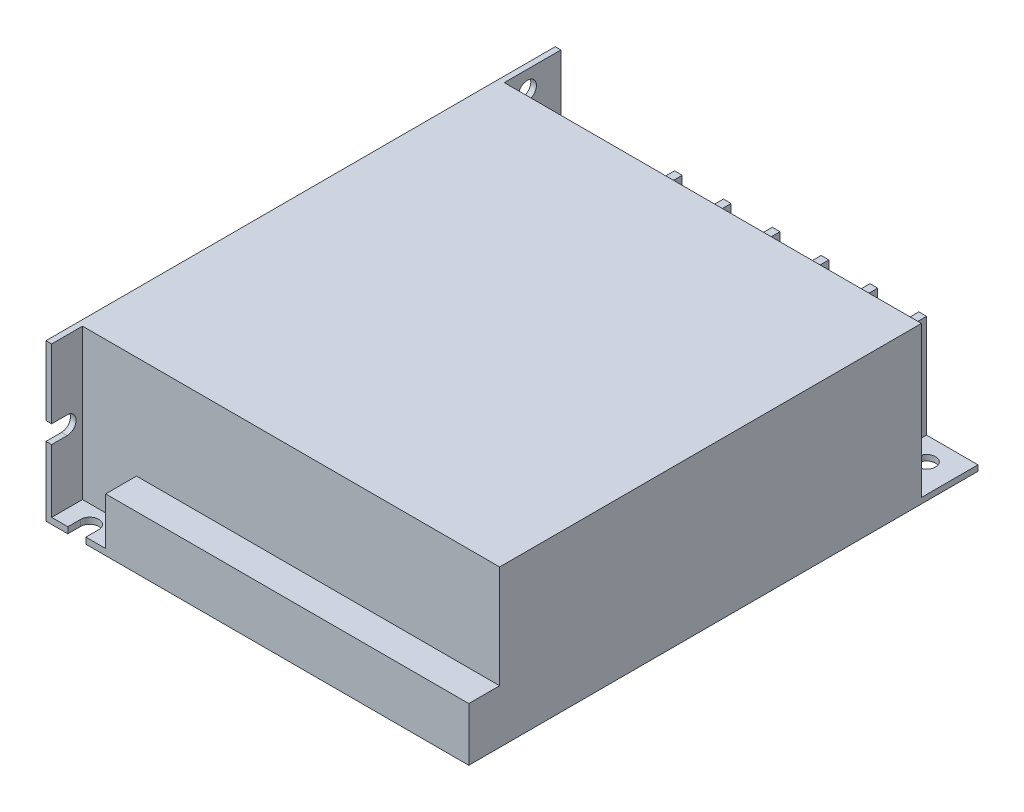
SolidWorks part; units mm, degrees
ref_plane "前基準面" through (0, 0, 0) normal (0, 0, 1) x (1, 0, 0)
ref_plane "上基準面" through (0, 0, 0) normal (0, 1, 0) x (1, 0, 0)
ref_plane "右基準面" through (0, 0, 0) normal (1, 0, 0) x (0, 0, -1)
sketch "草圖1" plane through (0, 0, 0) normal (0, 1, 0) x (1, 0, 0)
  line L1 (0, 0) -> (82.2, 0)
  line L2 (0, 0) -> (0, 99)
  line L3 (0, 99) -> (82.2, 99)
  line L4 (82.2, 0) -> (82.2, 99)
  dimension "D1" = 82.2
  dimension "D2" = 99
extrude "填料-伸長1" add sketch "草圖1" along normal blind 30.4
sketch "草圖3" plane through (0, 30.4, 0) normal (0, 1, 0) x (1, 0, 0)
  line L0 (0, 99) -> (0, 0) construction
  line L1 (82.2, 0) -> (1.1, 0)
  line L2 (82.2, 0) -> (82.2, 6)
  line L3 (82.2, 6) -> (1.1, 6)
  line L4 (1.1, 0) -> (1.1, 6)
  dimension "D1" = 6
  dimension "D2" = 1.1
extrude "除料-伸長1" cut sketch "草圖3" against normal blind 20
sketch "草圖4" plane through (0, 0, 0) normal (0, -1, 0) x (1, 0, 0)
  line L0 (0, -99) -> (0, 0) construction
  line L1 (0, 0) -> (82.2, 0) construction
  line L2 (82.2, -99) -> (0, -99) construction
  circle A0 centre (40.5, -23.5) radius 1.5
  circle A1 centre (40.5, -78.5) radius 1.5
  dimension "D4" = 3
  dimension "D5" = 3
  dimension "D1" = 40.5
  dimension "D2" = 23.5
  dimension "D3" = 20.5
extrude "除料-伸長2" cut sketch "草圖4" against normal blind 3
sketch "草圖5" plane through (0, 0, 0) normal (0, -1, 0) x (1, 0, 0)
  line L0 (82.2, -99) -> (0, -99) construction
  line L1 (82.2, 0) -> (82.2, -99) construction
  circle A0 centre (76.7, -94.5) radius 1.75
  dimension "D3" = 3.5
  dimension "D1" = 4.5
  dimension "D2" = 5.5
extrude "除料-伸長3" cut sketch "草圖5" against normal through all
sketch "草圖6" plane through (0, 30.4, 0) normal (0, 1, 0) x (1, 0, 0)
  line L1 (82.2, 99) -> (1.1, 99)
  line L2 (82.2, 99) -> (82.2, 88)
  line L3 (82.2, 88) -> (1.1, 88)
  line L4 (1.1, 99) -> (1.1, 88)
  line L5 (0, 99) -> (0, 0) construction
  dimension "D1" = 11
  dimension "D2" = 1.1
extrude "除料-伸長4" cut sketch "草圖6" against normal blind 29.3
sketch "草圖7" plane through (0, 0, 0) normal (-1, 0, 0) x (0, 0, 1)
  line L0 (0, 15.2) -> (-99, 15.2) construction
  line L1 (0, 30.4) -> (0, 0) construction
  line L2 (-99, 30.4) -> (-99, 0) construction
  line L3 (-3, 16.95) -> (0, 16.95)
  line L4 (0, 16.95) -> (0, 13.45)
  line L5 (0, 13.45) -> (-3, 13.45)
  circle A0 centre (-89, 15.2) radius 1.75
  circle A1 centre (-15, 15.2) radius 1.75
  arc A2 (-3, 16.95) -> (-3, 13.45) centre (-3, 15.2) ccw
  dimension "D1" = 3.5
  dimension "D2" = 3.5
  dimension "D5" = 3.5
  dimension "D3" = 15
  dimension "D4" = 10
  dimension "D6" = 3
extrude "除料-伸長5" cut sketch "草圖7" against normal blind 3
sketch "草圖8" plane through (0, 1.1, 0) normal (0, 1, 0) x (1, 0, 0)
  line L0 (82.2, 99) -> (1.1, 99) construction
  line L1 (72.2, 99) -> (23.2, 99)
  line L2 (72.2, 99) -> (72.2, 88)
  line L3 (72.2, 88) -> (23.2, 88)
  line L4 (23.2, 99) -> (23.2, 88)
  line L5 (1.1, 88) -> (82.2, 88) construction
  line L6 (82.2, 88) -> (82.2, 99) construction
  dimension "D1" = 49
  dimension "D2" = 10
extrude "填料-伸長2" add sketch "草圖8" along normal blind 20
sketch "草圖9" plane through (0, 1.1, 0) normal (0, 1, 0) x (1, 0, 0)
  line L1 (1.1, 99) -> (23.2, 99)
  line L2 (1.1, 99) -> (1.1, 88)
  line L3 (1.1, 88) -> (23.2, 88)
  line L4 (23.2, 99) -> (23.2, 88)
extrude "填料-伸長3" add sketch "草圖9" along normal blind 5.5
sketch "草圖10" plane through (0, 21.1, 0) normal (0, 1, 0) x (1, 0, 0)
  line L0 (72.2, 99) -> (23.2, 99) construction
  line L1 (24.7, 99) -> (32.7, 99)
  line L2 (24.7, 99) -> (24.7, 88)
  line L3 (24.7, 88) -> (32.7, 88)
  line L4 (32.7, 99) -> (32.7, 88)
  line L6 (34.2, 99) -> (42.2, 99)
  line L7 (34.2, 99) -> (34.2, 88)
  line L8 (34.2, 88) -> (42.2, 88)
  line L9 (42.2, 99) -> (42.2, 88)
  line L10 (43.7, 99) -> (51.7, 99)
  line L11 (43.7, 99) -> (43.7, 88)
  line L12 (43.7, 88) -> (51.7, 88)
  line L13 (51.7, 99) -> (51.7, 88)
  line L14 (53.2, 99) -> (61.2, 99)
  line L15 (53.2, 99) -> (53.2, 88)
  line L16 (53.2, 88) -> (61.2, 88)
  line L17 (61.2, 99) -> (61.2, 88)
  line L18 (62.7, 99) -> (70.7, 99)
  line L19 (62.7, 99) -> (62.7, 88)
  line L20 (62.7, 88) -> (70.7, 88)
  line L21 (70.7, 99) -> (70.7, 88)
  line L23 (82.2, 88) -> (1.1, 88)
  line L24 (23.2, 99) -> (23.2, 88) construction
  line M23 (72.2, 99) -> (23.2, 99)
  line M25 (23.2, 88) -> (72.2, 88)
  dimension "D1" = 8
  dimension "D2" = 8
  dimension "D3" = 8
  dimension "D4" = 8
  dimension "D5" = 8
  dimension "D6" = 1.5
  dimension "D7" = 1.5
  dimension "D8" = 1.5
  dimension "D9" = 1.5
  dimension "D10" = 1.5
extrude "除料-伸長6" cut sketch "草圖10" against normal blind 8 contours L21 L19 M23 M25 | L17 L15 M23 M25 | L13 L11 M23 M25 | L9 L7 M23 M25 | L4 L2 M23 M25 region at (28.7, 21.1, -93.5) region at (38.2, 21.1, -93.5) region at (47.7, 21.1, -93.5) region at (57.2, 21.1, -93.5) region at (66.7, 21.1, -93.5)
sketch "草圖11" plane through (0, 13.1, 0) normal (0, 1, 0) x (1, 0, 0)
  line L0 (62.7, 88) -> (70.7, 99) construction
  line L1 (53.2, 88) -> (61.2, 99) construction
  line L2 (70.7, 88) -> (62.7, 99) construction
  line L3 (53.2, 99) -> (61.2, 88) construction
  line L5 (43.7, 88) -> (51.7, 99) construction
  line L7 (43.7, 99) -> (51.7, 88) construction
  line L10 (34.2, 99) -> (42.2, 88) construction
  line L12 (34.2, 88) -> (42.2, 99) construction
  line L14 (24.7, 99) -> (32.7, 88) construction
  line L16 (24.7, 88) -> (32.7, 99) construction
  circle A0 centre (66.7, 93.5) radius 3.25
  circle A1 centre (57.2, 93.5) radius 3.25
  circle A2 centre (47.7, 93.5) radius 3.25
  circle A3 centre (38.2, 93.5) radius 3.25
  circle A4 centre (28.7, 93.5) radius 3.25
  dimension "D1" = 6.5
  dimension "D2" = 6.5
  dimension "D3" = 6.5
  dimension "D4" = 6.5
  dimension "D5" = 6.5
extrude "填料-伸長4" add sketch "草圖11" along normal blind 4.5
fillet "圓角1" radius 2 5 edges at (28.7, 17.6, -90.25) (38.2, 17.6, -90.25) (47.7, 17.6, -90.25) (57.2, 17.6, -90.25) (66.7, 17.6, -90.25)
sketch "草圖12" plane through (0, 0, 0) normal (-1, 0, 0) x (0, 0, 1)
  line L0 (-99, 30.4) -> (-99, 0) construction
  line L1 (-99, 30.4) -> (0, 30.4) construction
  circle A0 centre (-92.5, 26.8) radius 1.75
  point P6 (-96.2868, 25.2584)
  dimension "D3" = 3.5
  dimension "D1" = 6.5
  dimension "D2" = 3.6
extrude "除料-伸長7" cut sketch "草圖12" against normal blind 4.5
sketch "草圖13" plane through (0, 10.4, 0) normal (0, 1, 0) x (1, 0, 0)
  line L0 (82.2, 6) -> (1.1, 6) construction
  line L1 (1.1, 0) -> (11.6, 0)
  line L2 (1.1, 0) -> (1.1, 6)
  line L3 (1.1, 6) -> (11.6, 6)
  line L4 (11.6, 0) -> (11.6, 6)
  dimension "D1" = 10.5
extrude "除料-伸長8" cut sketch "草圖13" against normal blind 9.2
sketch "草圖14" plane through (0, 0, 0) normal (0, -1, 0) x (1, 0, 0)
  line L0 (0, -99) -> (0, 0) construction
  line L1 (0, 0) -> (82.2, 0) construction
  line L2 (7.75, -2.5) -> (7.75, 0)
  line L3 (7.75, 0) -> (4.25, 0)
  line L4 (4.25, 0) -> (4.25, -2.5)
  arc A0 (4.25, -2.5) -> (7.75, -2.5) centre (6, -2.5) ccw
  dimension "D1" = 3.5
  dimension "D2" = 6
  dimension "D3" = 2.5
extrude "除料-伸長9" cut sketch "草圖14" against normal through all
